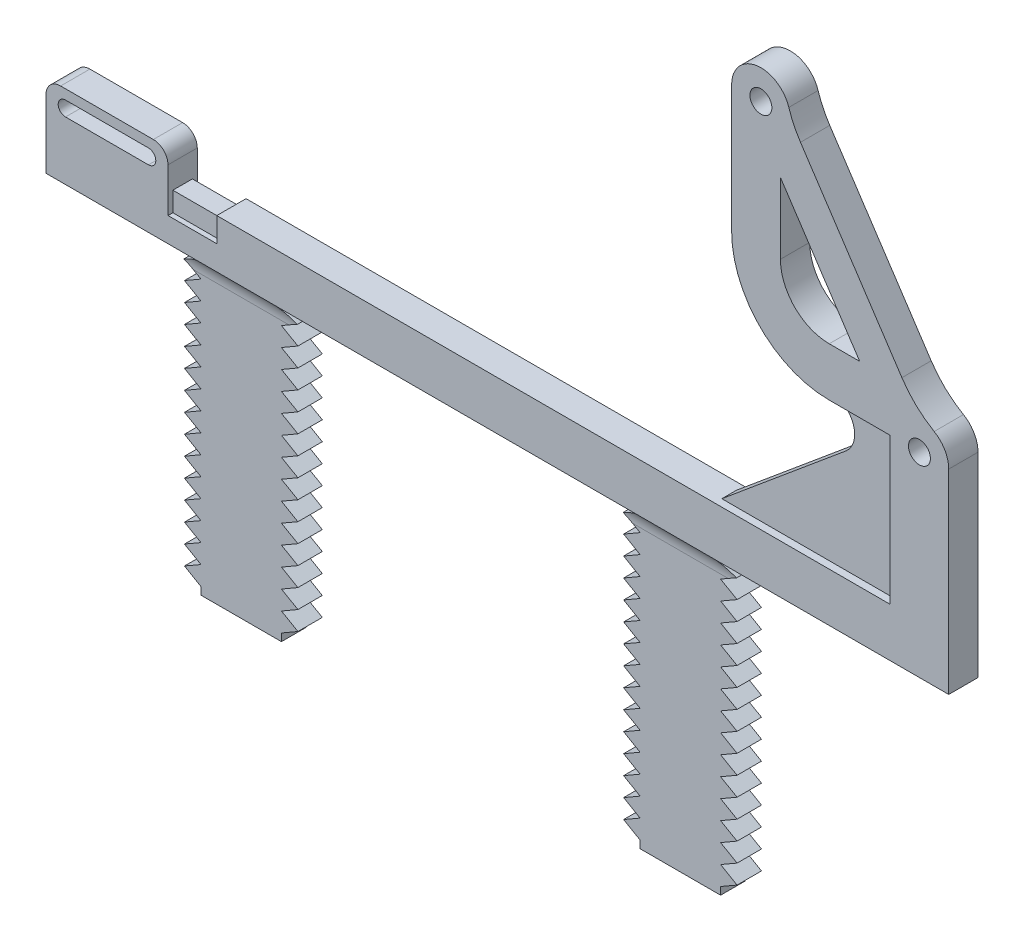
SolidWorks part; units mm, degrees
ref_plane "Front Plane" through (0, 0, 0) normal (0, 0, 1) x (1, 0, 0)
ref_plane "Top Plane" through (0, 0, 0) normal (0, 1, 0) x (1, 0, 0)
ref_plane "Right Plane" through (0, 0, 0) normal (1, 0, 0) x (0, 0, -1)
sketch "Sketch1" plane through (0, 0, 0) normal (0, 0, 1) x (1, 0, 0)
  line L0 (0, 0) -> (-32.49, 0) construction
  line L1 (-6, 0) -> (6, 0) construction
  line L2 (-6, 0) -> (-6, -40)
  line L3 (-6, -40) -> (6, -40)
  line L4 (6, 0) -> (6, -40)
  line L5 (-32.49, 0) -> (-32.49, 46) construction
  line L6 (-38.49, 46) -> (-38.49, 0)
  line L7 (-38.49, 0) -> (-6, 0)
  line L8 (-26.49, 46) -> (0, 6)
  line L9 (-28.49, 34.5311) -> (-12.2442, 10)
  line L10 (-12.2442, 10) -> (-28.49, 10)
  line L11 (-28.49, 10) -> (-28.49, 34.5311)
  circle A0 centre (0, 0) radius 2.25
  arc A1 (6, 0) -> (0, 6) centre (0, 0) ccw
  circle A2 centre (-32.49, 46) radius 2.25
  arc A3 (-26.49, 46) -> (-38.49, 46) centre (-32.49, 46) ccw
  dimension "D1" = 4.5
  dimension "D2" = 12
  dimension "D6" = 4.5
  dimension "D7" = 12
  dimension "D3" = 40
  dimension "D4" = 32.49
  dimension "D5" = 46
  dimension "D8" = 8
  dimension "D9" = 10
  dimension "D10" = 10
extrude "Boss-Extrude1" add sketch "Sketch1" along normal blind 6
sketch "Sketch2" plane through (0, 0, 0) normal (0, 0, 1) x (1, 0, 0)
  line L0 (-175, -26.5) -> (-158, -26.5) construction
  line L1 (6, -40) -> (-179, -40)
  line L2 (6, -40) -> (6, -30)
  line L3 (6, -30) -> (-154, -30)
  line L4 (-179, -40) -> (-179, -30)
  line L6 (-179, -30) -> (-179, -23)
  line L7 (-179, -23) -> (-154, -23)
  line L8 (-154, -30) -> (-154, -23)
  line L9 (-175, -25) -> (-158, -25)
  line L10 (-175, -28) -> (-158, -28)
  arc A0 (-175, -25) -> (-175, -28) centre (-175, -26.5) ccw
  arc A1 (-158, -28) -> (-158, -25) centre (-158, -26.5) ccw
  point P10 (-166.5, -26.5)
  point P16 (-154, -26.5)
  point P18 (-166.5, -23)
  dimension "D1" = 10
  dimension "D2" = 185
  dimension "D3" = 25
  dimension "D4" = 3
  dimension "D5" = 17
  dimension "D6" = 2
extrude "Boss-Extrude2" add sketch "Sketch2" along normal blind 6
fillet "Fillet1" radius 3 2 edges at (-179, -23, 3) (-154, -23, 3)
sketch "Sketch3" plane through (0, 0, 6) normal (0, 0, 1) x (1, 0, 0)
  line L1 (-6, 0) -> (-42, -30)
  line L2 (-6, -30) -> (-154, -30) construction
  line L3 (-42, -30) -> (-6, -30)
  line L4 (-6, 0) -> (-6, -30) construction
  line L5 (-6, 0) -> (-6, -30)
  dimension "D1" = 36
extrude "Boss-Extrude3" add sketch "Sketch3" along normal blind 3 from offset 4.5 offset against normal yes
sketch "Sketch4" plane through (-154, 0, 0) normal (1, 0, 0) x (0, 0, -1)
  line L0 (0, -40) -> (0, 0) construction
  line L1 (-6, -30) -> (0, -30)
  line L2 (-6, -30) -> (-6, -35)
  line L3 (-6, -35) -> (-5, -35)
  line L4 (0, -30) -> (0, -35)
  line L5 (-5, -34) -> (-1, -34) construction
  line L6 (-1, -31) -> (-1, -34)
  line L7 (-5, -31) -> (-1, -31)
  line L8 (-5, -31) -> (-5, -34)
  line L9 (-5, -34) -> (-5, -35)
  line L10 (-1, -34) -> (-1, -40)
  line L11 (-6, -40) -> (0, -40) construction
  line L12 (-6, -35) -> (0, -35) construction
  line L13 (0, -35) -> (0, -40)
  line L14 (0, -40) -> (-1, -40)
  dimension "D1" = 1
  dimension "D2" = 5
extrude "Cut-Extrude1" cut sketch "Sketch4" along normal blind 10
fillet "Fillet2" radius 20 1 edges at (-38.49, 0, 3)
fillet "Fillet3" radius 5 1 edges at (-6, 0, 3) tangent propagation no
fillet "Fillet4" radius 20 2 edges at (0, 6, 3) (-26.49, 46, 3)
fillet "Fillet5" radius 10 1 edges at (-28.49, 10, 3)
sketch "Sketch5" plane through (0, 0, 0) normal (0, 0, 1) x (1, 0, 0)
  line L0 (-179, -40) -> (6, -40) construction
  line L1 (-179, -40) -> (6, -40) construction
  line L2 (-50, -40) -> (-50, -69.654) construction
  line L3 (0, 0) -> (0, -70) construction
  line L4 (-119.6056, -70) -> (64.6682, -70) construction
  line L5 (-58.25, -40) -> (-61.625, -41.9486)
  line L6 (-58.25, -40) -> (-41.75, -40)
  line L8 (-58.25, -100) -> (-41.75, -100)
  line L9 (-41.75, -40) -> (-41.75, -90.6625) construction
  line L10 (-61.625, -41.9486) -> (-58.25, -43.8971)
  line L11 (-58.25, -43.8971) -> (-58.25, -40) construction
  line L12 (-58.25, -43.8971) -> (-58.25, -90.6625) construction
  line L13 (-61.625, -41.9486) -> (-61.625, -86.7031) construction
  line L14 (-58.25, -43.8971) -> (-61.625, -45.8457)
  line L15 (-61.625, -45.8457) -> (-58.25, -47.7942)
  line L16 (-58.25, -47.7942) -> (-61.625, -49.7428)
  line L17 (-61.625, -49.7428) -> (-58.25, -51.6913)
  line L18 (-58.25, -51.6913) -> (-61.625, -53.6399)
  line L19 (-61.625, -53.6399) -> (-58.25, -55.5885)
  line L20 (-58.25, -55.5885) -> (-61.625, -57.537)
  line L21 (-61.625, -57.537) -> (-58.25, -59.4856)
  line L22 (-58.25, -59.4856) -> (-61.625, -61.4341)
  line L23 (-61.625, -61.4341) -> (-58.25, -63.3827)
  line L24 (-58.25, -63.3827) -> (-61.625, -65.3312)
  line L25 (-61.625, -65.3312) -> (-58.25, -67.2798)
  line L26 (-58.25, -67.2798) -> (-61.625, -69.2284)
  line L27 (-61.625, -69.2284) -> (-58.25, -71.1769)
  line L28 (-58.25, -71.1769) -> (-61.625, -73.1255)
  line L29 (-61.625, -73.1255) -> (-58.25, -75.074)
  line L30 (-58.25, -75.074) -> (-61.625, -77.0226)
  line L31 (-61.625, -77.0226) -> (-58.25, -78.9711)
  line L32 (-58.25, -78.9711) -> (-61.625, -80.9197)
  line L33 (-61.625, -80.9197) -> (-58.25, -82.8683)
  line L34 (-58.25, -82.8683) -> (-61.625, -84.8168)
  line L35 (-61.625, -84.8168) -> (-58.25, -86.7654)
  line L36 (-58.25, -86.7654) -> (-61.625, -88.7139)
  line L37 (-61.625, -88.7139) -> (-58.25, -90.6625)
  line L38 (-58.25, -98.4567) -> (-58.25, -100)
  line L39 (-41.75, -98.4567) -> (-41.75, -100)
  line L40 (-38.375, -88.7139) -> (-41.75, -90.6625)
  line L41 (-41.75, -86.7654) -> (-38.375, -88.7139)
  line L42 (-38.375, -84.8168) -> (-41.75, -86.7654)
  line L43 (-41.75, -82.8683) -> (-38.375, -84.8168)
  line L44 (-38.375, -80.9197) -> (-41.75, -82.8683)
  line L45 (-41.75, -78.9711) -> (-38.375, -80.9197)
  line L46 (-38.375, -77.0226) -> (-41.75, -78.9711)
  line L47 (-41.75, -75.074) -> (-38.375, -77.0226)
  line L48 (-38.375, -73.1255) -> (-41.75, -75.074)
  line L49 (-41.75, -71.1769) -> (-38.375, -73.1255)
  line L50 (-38.375, -69.2284) -> (-41.75, -71.1769)
  line L51 (-41.75, -67.2798) -> (-38.375, -69.2284)
  line L52 (-38.375, -65.3312) -> (-41.75, -67.2798)
  line L53 (-41.75, -63.3827) -> (-38.375, -65.3312)
  line L54 (-38.375, -61.4341) -> (-41.75, -63.3827)
  line L55 (-41.75, -59.4856) -> (-38.375, -61.4341)
  line L56 (-38.375, -57.537) -> (-41.75, -59.4856)
  line L57 (-41.75, -55.5885) -> (-38.375, -57.537)
  line L58 (-38.375, -53.6399) -> (-41.75, -55.5885)
  line L59 (-41.75, -51.6913) -> (-38.375, -53.6399)
  line L60 (-38.375, -49.7428) -> (-41.75, -51.6913)
  line L61 (-41.75, -47.7942) -> (-38.375, -49.7428)
  line L62 (-38.375, -45.8457) -> (-41.75, -47.7942)
  line L63 (-41.75, -43.8971) -> (-38.375, -45.8457)
  line L64 (-38.375, -41.9486) -> (-41.75, -43.8971)
  line L65 (-41.75, -40) -> (-38.375, -41.9486)
  line L66 (-58.25, -90.6625) -> (-61.625, -92.611)
  line L67 (-61.625, -92.611) -> (-58.25, -94.5596)
  line L68 (-41.75, -90.6625) -> (-38.375, -92.611)
  line L69 (-38.375, -92.611) -> (-41.75, -94.5596)
  line L70 (-58.25, -94.5596) -> (-61.625, -96.5082)
  line L71 (-61.625, -96.5082) -> (-58.25, -98.4567)
  line L72 (-41.75, -94.5596) -> (-38.375, -96.5082)
  line L73 (-38.375, -96.5082) -> (-41.75, -98.4567)
  line L74 (-41.75, -98.4567) -> (-41.75, -100) construction
  point P13 (-50, -100)
  dimension "D1" = 50
  dimension "D2" = 30
  dimension "D3" = 8.25
  dimension "D4" = 3.375
  dimension "D5" = 13
  dimension "D6" = 30
  dimension "D7" = 3
extrude "Boss-Extrude5" add sketch "Sketch5" along normal blind 5
pattern_linear "LPattern1" count 2 spacing 90 along (-1, 0, 0) of "Boss-Extrude5"
fillet "Fillet6" radius 5 2 edges at (-50, -40, 5) (-140, -40, 5)
